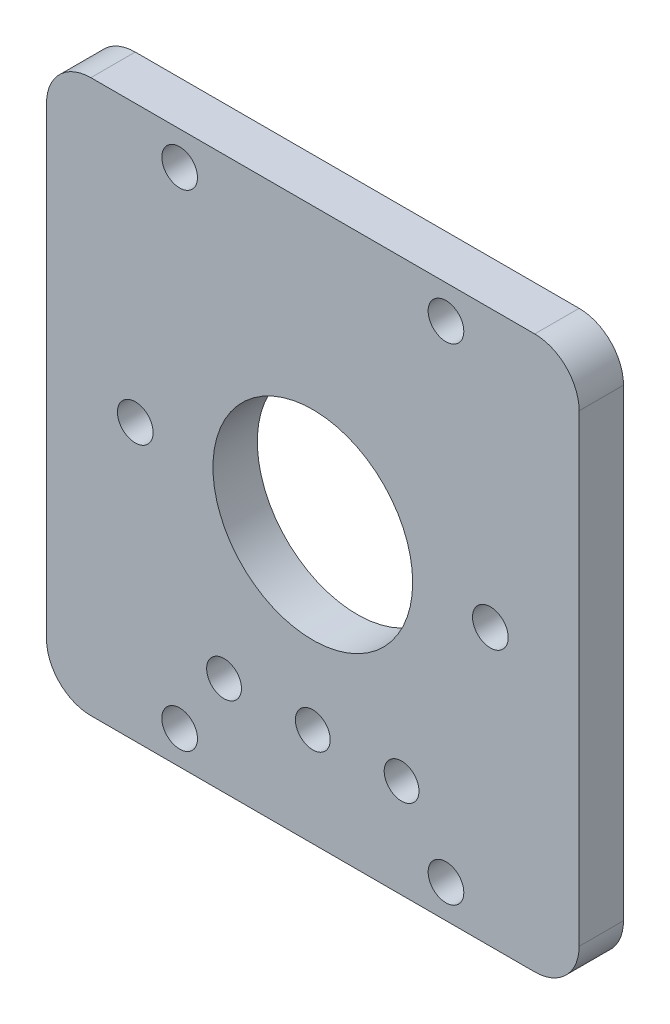
SolidWorks part; units mm, degrees
material "6061-T6 (SS)"
ref_plane "Front Plane" through (0, 0, 0) normal (0, 0, 1) x (1, 0, 0)
ref_plane "Top Plane" through (0, 0, 0) normal (0, 1, 0) x (1, 0, 0)
ref_plane "Right Plane" through (0, 0, 0) normal (1, 0, 0) x (0, 0, -1)
sketch "Sketch5" plane through (0, 0, 0) normal (0, 0, 1) x (1, 0, 0)
  line L0 (-19.7318, -15.9943) -> (19.7318, 15.9943) construction
  line L1 (0, 0) -> (25.4, 0) construction
  line L2 (-19.05, 34.7624) -> (19.05, 34.7624) construction
  line L3 (-38.1, -39.5249) -> (38.1, -39.5249)
  line L4 (-38.1, -39.5249) -> (-38.1, 39.5249)
  line L5 (-38.1, 39.5249) -> (38.1, 39.5249)
  line L6 (38.1, -39.5249) -> (38.1, 39.5249)
  line L7 (-38.1, -39.5249) -> (38.1, 39.5249) construction
  line L8 (-38.1, 39.5249) -> (38.1, -39.5249) construction
  line L9 (-38.1, 0) -> (38.1, 0) construction
  line L10 (-19.05, -34.7624) -> (19.05, -34.7624) construction
  line L11 (-12.7, -25.4) -> (12.7, -25.4) construction
  line L12 (25.4, -39.5249) -> (-29.5586, -39.5249)
  line L16 (-38.1, -12.7) -> (38.1, -12.7) construction
  line L17 (-38.1, -12.7) -> (-38.1, 12.7) construction
  line L18 (-38.1, 12.7) -> (38.1, 12.7) construction
  line L19 (38.1, -12.7) -> (38.1, 12.7) construction
  line L20 (-38.1, -12.7) -> (38.1, 12.7) construction
  line L21 (-38.1, 12.7) -> (38.1, -12.7) construction
  circle A0 centre (0, 0) radius 14.2875
  circle A1 centre (0, 0) radius 25.4 construction
  circle A2 centre (-19.7318, -15.9943) radius 2.5527
  circle A3 centre (19.7318, 15.9943) radius 2.5527
  circle A6 centre (-19.05, 34.7624) radius 2.5527
  circle A7 centre (19.05, 34.7624) radius 2.5527
  circle A8 centre (19.05, -34.7624) radius 2.5527
  circle A9 centre (-19.05, -34.7624) radius 2.5527
  circle A13 centre (-25.4, 0) radius 2.5527
  circle A14 centre (25.4, 0) radius 2.5527
  circle A15 centre (-12.7, -25.4) radius 2.4892
  circle A16 centre (12.7, -25.4) radius 2.4892
  circle A17 centre (0, -25.4) radius 2.4892
  point P8 (0, 0)
  point P19 (0, 34.7624)
  point P37 (0, -25.4)
  dimension "D1" = 28.575
  dimension "D2" = 5.1054
  dimension "D3" = 50.8
  dimension "D5" = 19.05
  dimension "D6" = 5.1054
  dimension "D8" = 76.2
  dimension "D11" = 12.7
  dimension "D12" = 12.7
  dimension "D14" = 5.1054
  dimension "D10" = 4.9784
  dimension "D4" = 34.7624
  dimension "45" = 39.028
  dimension "D7" = 4.7625
  dimension "D9" = 25.4
extrude "Boss-Extrude1" add sketch "Sketch5" along normal blind 6.35 contours L3 L6 L5 L4 A14 A13 A8 A7 A6 A3 A2 A0 A9 | L3 | A2 | A3 region at (-37.002, 0, 0) region at (-19.7318, -15.9943, 0) region at (19.7318, 15.9943, 0)
fillet "Fillet2" radius 6.35 4 edges at (-38.1, -39.5249, 3.175) (38.1, -39.5249, 3.175) (38.1, 39.5249, 3.175) (-38.1, 39.5249, 3.175)
equation "\"NEO\"= 60mm"
